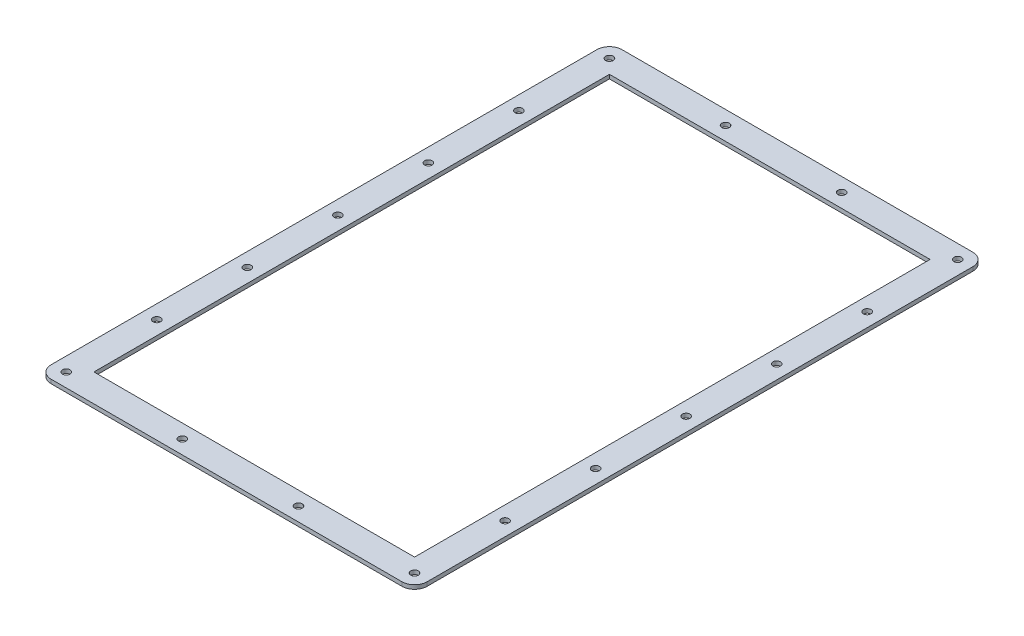
SolidWorks part; units mm, degrees
material "5052-H32"
ref_plane "Front Plane" through (0, 0, 0) normal (0, 0, 1) x (1, 0, 0)
ref_plane "Top Plane" through (0, 0, 0) normal (0, 1, 0) x (1, 0, 0)
ref_plane "Right Plane" through (0, 0, 0) normal (1, 0, 0) x (0, 0, -1)
sketch "Sketch1" plane through (0, 0, 0) normal (0, 1, 0) x (1, 0, 0)
  line L0 (-147, 182) -> (152, 182)
  line L1 (-125, -250) -> (130, -250)
  line L2 (-125, -250) -> (-125, 160)
  line L3 (-125, 160) -> (130, 160)
  line L4 (130, -250) -> (130, 160)
  line L5 (-125, -250) -> (130, 160) construction
  line L6 (-125, 160) -> (130, -250) construction
  line L7 (152, -272) -> (152, 182)
  line L8 (-147, -272) -> (152, -272)
  line L9 (-147, -272) -> (-147, 182)
  line L12 (130, -45) -> (-125, -45) construction
  circle A34 centre (141, 171) radius 3
  circle A35 centre (48.6667, 171) radius 3
  circle A36 centre (-43.6667, 171) radius 3
  circle A37 centre (-136, 171) radius 3
  circle A90 centre (141, 99) radius 3
  circle A91 centre (141, 27) radius 3
  circle A92 centre (141, -45) radius 3
  circle A93 centre (141, -117) radius 3
  circle A94 centre (141, -189) radius 3
  circle A102 centre (-136, 99) radius 3
  circle A103 centre (141, -261) radius 3
  circle A106 centre (-136, 27) radius 3
  circle A107 centre (48.6667, -261) radius 3
  circle A110 centre (-136, -45) radius 3
  circle A111 centre (-43.6667, -261) radius 3
  circle A114 centre (-136, -117) radius 3
  circle A115 centre (-136, -261) radius 3
  circle A118 centre (-136, -189) radius 3
  circle A119 centre (48.6667, -117) radius 3 [skipped]
  circle A120 centre (-43.6667, -117) radius 3 [skipped]
  circle A121 centre (48.6667, 99) radius 3 [skipped]
  circle A122 centre (-43.6667, 99) radius 3 [skipped]
  circle A123 centre (48.6667, 27) radius 3 [skipped]
  circle A124 centre (48.6667, -45) radius 3 [skipped]
  circle A125 centre (-43.6667, -45) radius 3 [skipped]
  circle A126 centre (-43.6667, 27) radius 3 [skipped]
  circle A127 centre (48.6667, -189) radius 3 [skipped]
  circle A128 centre (-43.6667, -189) radius 3 [skipped]
  dimension "D4" = 6
  dimension "D2" = 410
  dimension "D1" = 22
  dimension "D3" = 255
  dimension "D5" = 11
  dimension "D6" = 11
  dimension "D9" = 72
  dimension "D10" = 92.3333
  dimension "D7" = 4
  dimension "D8" = 7
extrude "Boss-Extrude1" add sketch "Sketch1" along normal blind 3.175 contours L9 L8 L7 L0 L4 L1 L2 L3 A34 region at (2.5, 0, -176.5639)
fillet "Fillet1" radius 10 4 edges at (152, 1.5875, 272) (-147, 1.5875, 272) (152, 1.5875, -182) (-147, 1.5875, -182)
equation "\"L\"= 410mm"
equation "\"W\"= 255mm"
equation "\"H\"= 110mm"
equation "\"Compartment Width\"= 80"
equation "\"T\"= 4.7625 * 2 / 3mm"
equation "\"Inside Fillet Radius\"= 5.55625mm"
equation "\"Hole\"=15mm"
equation "\"D2@Sketch1\"=\"L\""
equation "\"D1@Boss-Extrude1\"=\"T\""
equation "\"D3@Sketch1\"=\"W\""
equation "\"D9@Sketch1\"=(\"L\"+22)/6"
equation "\"D10@Sketch1\"=(\"W\"+22)/3"
equation "\"Offset\"= 13mm"
equation "\"Wheel to Wall\"= 43"
